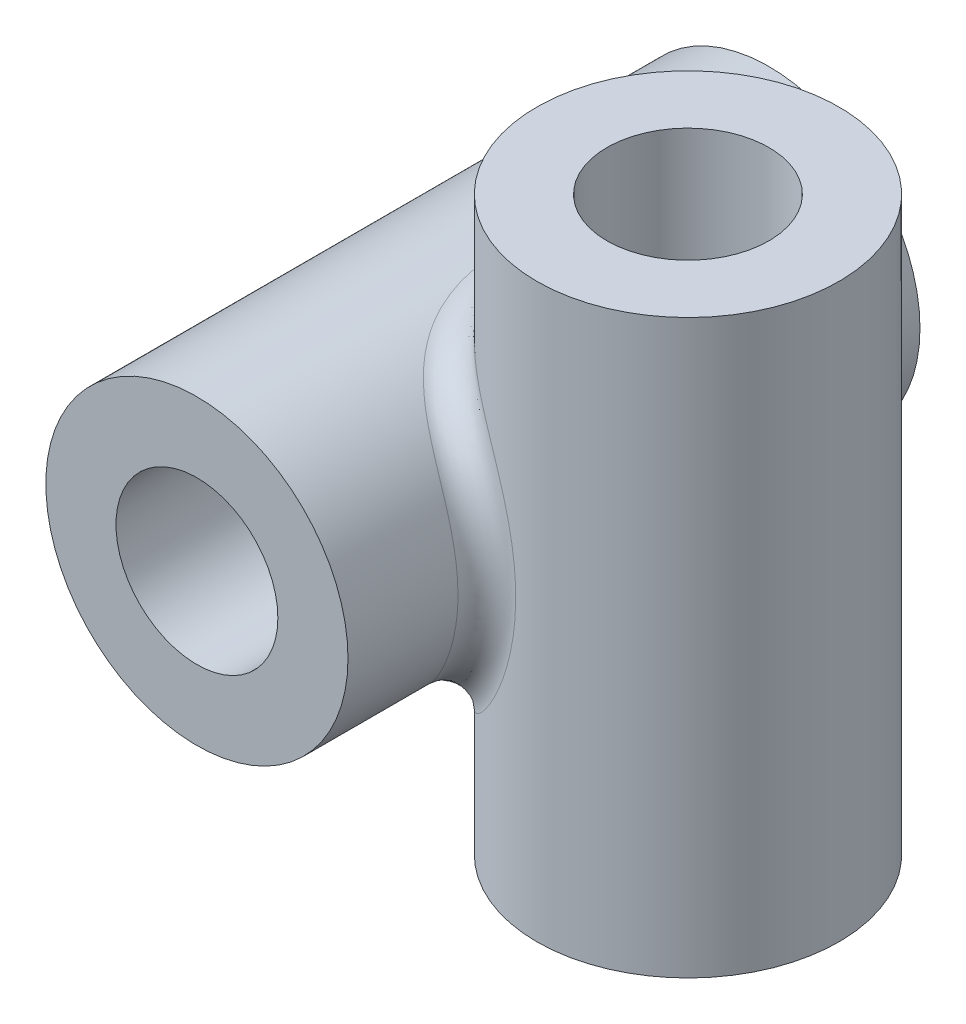
SolidWorks part; units mm, degrees
material "Gray Cast Iron"
ref_plane "Front Plane" through (0, 0, 0) normal (0, 0, 1) x (1, 0, 0)
ref_plane "Top Plane" through (0, 0, 0) normal (0, 1, 0) x (1, 0, 0)
ref_plane "Right Plane" through (0, 0, 0) normal (1, 0, 0) x (0, 0, -1)
sketch "Sketch1" plane through (0, 0, 0) normal (0, 0, 1) x (1, 0, 0)
  circle A0 centre (0, 0) radius 28
  circle A1 centre (0, 0) radius 15
  dimension "D1" = 30
  dimension "D2" = 56
extrude "Boss-Extrude1" add sketch "Sketch1" along normal mid plane 106
sketch "Sketch2" plane through (0, 0, 0) normal (0, 1, 0) x (1, 0, 0)
  circle A0 centre (38, 0) radius 28
  circle A1 centre (38, 0) radius 15
  point P3 (0, 0)
  point P6 (0, 0)
  dimension "D1" = 56
  dimension "D2" = 30
  dimension "D3" = 38
extrude "Boss-Extrude2" add sketch "Sketch2" along normal mid plane 106
sketch "Sketch8" plane through (0, 53, 0) normal (0, 1, 0) x (1, 0, 0)
  arc A0 (28, 11.1803) -> (28, -11.1803) centre (38, 0) ccw construction
  circle A1 centre (38, 0) radius 28
  circle A2 centre (38, 0) radius 28
  arc A3 (28, 11.1803) -> (28, -11.1803) centre (38, 0) ccw
  circle M2 centre (38, 0) radius 28
  circle M3 centre (38, 0) radius 15
  dimension "D1" = 0
extrude "Cut-Extrude3" cut sketch "Sketch8" against normal blind 106 contours M3 M2 region at (38, 53, 0)
sketch "Sketch9" plane through (0, 0, -53) normal (0, 0, -1) x (-1, 0, 0)
  arc A0 (-10, 11.1803) -> (-10, -11.1803) centre (0, 0) ccw construction
  circle A1 centre (0, 0) radius 28
  circle A2 centre (0, 0) radius 28
  arc A3 (-10, 11.1803) -> (-10, -11.1803) centre (0, 0) ccw
  circle M3 centre (0, 0) radius 15
  dimension "D1" = 0
extrude "Cut-Extrude4" cut sketch "Sketch9" against normal blind 106 contours M3 region at (0, 0, -53)
fillet "Fillet1" radius 5 1 edges at (28, -0.0242, -26.1534)
